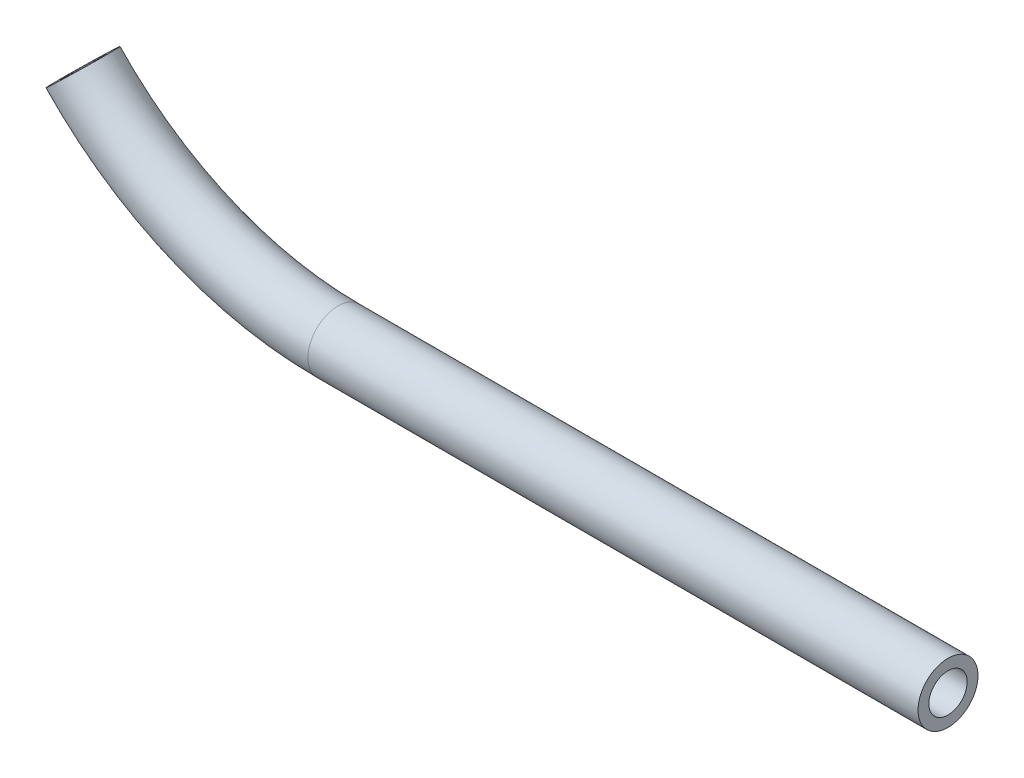
SolidWorks part; units mm, degrees
ref_plane "Front Plane" through (0, 0, 0) normal (0, 0, 1) x (1, 0, 0)
ref_plane "Top Plane" through (0, 0, 0) normal (0, 1, 0) x (1, 0, 0)
ref_plane "Right Plane" through (0, 0, 0) normal (1, 0, 0) x (0, 0, -1)
ref_axis "Axis1" through (-88.99, 0, 0) along (1, 0, 0)
sketch "Sketch4" plane through (0, 0, 0) normal (0, 0, 1) x (1, 0, 0)
  line L0 (-218.053, 283.5718) -> (61.923, 683.419) construction
  line L1 (-68.365, 0) -> (-65.9542, 0)
  arc A0 (-68.365, 0) -> (-73.5499, 2.2253) centre (-68.365, 7.1532) cw
  point P2 (-73.5499, 2.2253)
  point P3 (-68.365, 0)
sketch "Sketch1" plane through (0, 0, 0) normal (1, 0, 0) x (0, 0, -1)
  circle A0 centre (0, 0) radius 0.61
  circle A1 centre (0, 0) radius 0.39
  dimension "D1" = 1.22
  dimension "D2" = 0.22
extrude "Boss-Extrude1" [suppressed] add sketch "Sketch1" along normal blind 10
ref_plane "Plane1" through (-65.9542, 0, 0) normal (1, 0, 0) x (0, 0, -1)
sketch "Sketch5" plane through (-65.9542, 0, 0) normal (1, 0, 0) x (0, 0, -1)
  circle A0 centre (0, 0) radius 0.61
  circle A1 centre (0, 0) radius 0.39
  dimension "D1" = 1.22
  dimension "D2" = 0.22
sweep "Sweep2" add profiles "Sketch5" path "Sketch4"
extrude "Boss-Extrude2" add sketch "Sketch5<2>" along normal blind 10
sketch "Sketch5<2>" plane through (-65.9542, 0, 0) normal (1, 0, 0) x (0, 0, -1) same geometry as "Sketch5"
